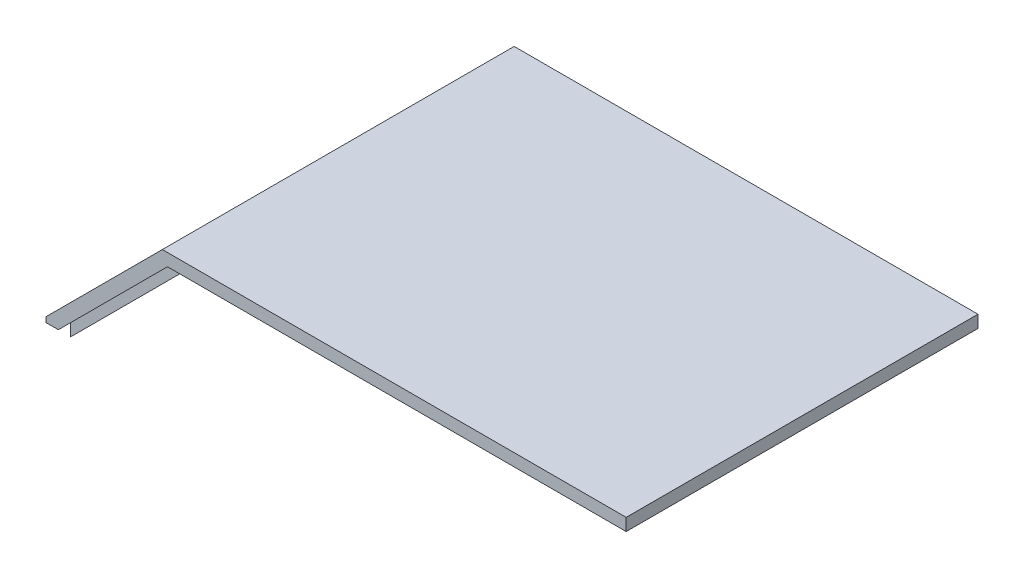
SolidWorks part; units mm, degrees
ref_plane "Front Plane" through (0, 0, 0) normal (0, 0, 1) x (1, 0, 0)
ref_plane "Top Plane" through (0, 0, 0) normal (0, 1, 0) x (1, 0, 0)
ref_plane "Right Plane" through (0, 0, 0) normal (1, 0, 0) x (0, 0, -1)
sketch "Sketch1" plane through (0, 0, 0) normal (0, 0, 1) x (1, 0, 0)
  line L0 (0, 0) -> (35.3553, 35.3553)
  line L1 (0, 0) -> (20.6791, 0) construction
  line L2 (35.3553, 35.3553) -> (184, 35.3553)
  line L3 (184, 35.3553) -> (184, 39.3553)
  line L4 (0, 0) -> (-4, 0)
  line L6 (33.6985, 39.3553) -> (184, 39.3553)
  line L7 (33.6985, 39.3553) -> (-4, 1.6569)
  line L8 (-4, 1.6569) -> (-4, 0)
  dimension "D1" = 50
  dimension "D2" = 45
  dimension "D3" = 184
  dimension "D4" = 4
  dimension "D5" = 4
  dimension "D6" = 4
extrude "Boss-Extrude1" add sketch "Sketch1" against normal blind 114 contours L6 L3 L2 L0 L4 L8 L7
sketch "Sketch3" plane through (0, 35.3553, 0) normal (0, -1, 0) x (1, 0, 0)
  line L0 (180, -4) -> (35.3553, -4)
  line L1 (35.3553, -114) -> (35.3553, 0) construction
  line L2 (35.3553, -4) -> (35.3553, -6)
  line L3 (35.3553, -6) -> (178, -6)
  line L4 (178, -6) -> (178, -108)
  line L5 (178, -108) -> (35.3553, -108)
  line L6 (35.3553, -108) -> (35.3553, -110)
  line L7 (35.3553, -110) -> (180, -110)
  line L8 (180, -110) -> (180, -4)
  line L9 (35.3553, 0) -> (184, 0) construction
  line L10 (184, -114) -> (184, 0) construction
  line L11 (35.3553, -114) -> (184, -114) construction
  dimension "D1" = 4
  dimension "D2" = 4
  dimension "D3" = 4
  dimension "D4" = 2
  dimension "D5" = 2
  dimension "D6" = 2
extrude "Boss-Extrude2" add sketch "Sketch3" along normal blind 4
sketch "Sketch5" plane through (0, 0, 0) normal (0.7071, -0.7071, 0) x (0, 0, -1)
  line L0 (4, 50) -> (4, 0)
  line L1 (114, 0) -> (0, 0) construction
  line L3 (6, 3) -> (6, 50)
  line L4 (108, 50) -> (108, 3)
  line L6 (110, 0) -> (110, 50)
  line L7 (4, 50) -> (6, 50)
  line L8 (108, 50) -> (110, 50)
  line L9 (4, 0) -> (110, 0)
  line L10 (6, 3) -> (108, 3)
  dimension "D1" = 3
extrude "Boss-Extrude3" add sketch "Sketch5" along direction (0, 1, 0) on the side of the normal blind 4 contours L10 L4 L8 L6 L9 L0 L7 L3
